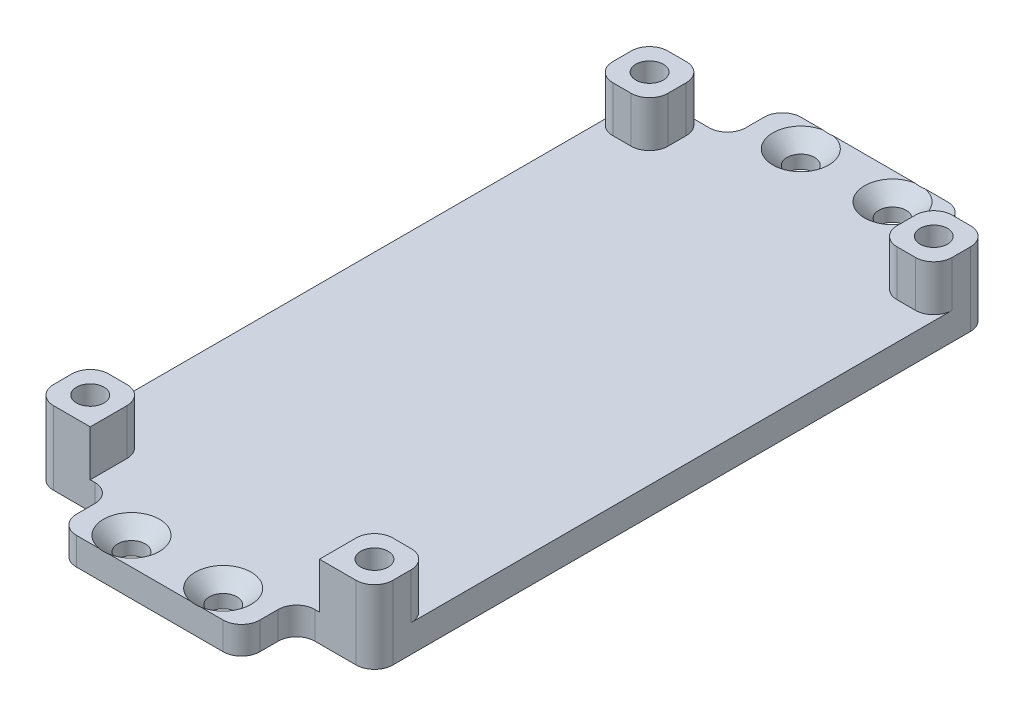
SolidWorks part; units mm, degrees
ref_plane "Front Plane" through (0, 0, 0) normal (0, 0, 1) x (1, 0, 0)
ref_plane "Top Plane" through (0, 0, 0) normal (0, 1, 0) x (1, 0, 0)
ref_plane "Right Plane" through (0, 0, 0) normal (1, 0, 0) x (0, 0, -1)
sketch "Sketch1" plane through (0, 0, 0) normal (0, 1, 0) x (1, 0, 0)
  line L0 (-36, 33) -> (0, 33) construction
  line L1 (0, 0) -> (-36, 0) construction
  line L2 (0, 0) -> (0, 66) construction
  line L3 (0, 66) -> (-36, 66) construction
  line L4 (-36, 0) -> (-36, 66) construction
  line L5 (-36.5, 66.5) -> (0.5, 66.5)
  line L6 (-36.5, 66.5) -> (-36.5, -0.5)
  line L7 (-36.5, -0.5) -> (0.5, -0.5)
  line L8 (0.5, 66.5) -> (0.5, -0.5)
  line L9 (-18, 66) -> (-18, 0) construction
  line L10 (-2.5, 63.5) -> (-33.5, 63.5) construction
  line L11 (-33.5, 2.5) -> (-33.5, 63.5) construction
  line L12 (-2.5, 2.5) -> (-33.5, 2.5) construction
  line L13 (-2.5, 2.5) -> (-2.5, 63.5) construction
  circle A4 centre (-2.5, 63.5) radius 1.5
  circle A5 centre (-33.5, 63.5) radius 1.5
  circle A6 centre (-2.5, 2.5) radius 1.5
  circle A7 centre (-33.5, 2.5) radius 1.5
  point P8 (0, 0)
  point P22 (0, 0)
  dimension "D3" = 3
  dimension "D1" = 66
  dimension "D2" = 36
  dimension "D4" = 67
  dimension "D5" = 37
  dimension "D6" = 2.5
extrude "Boss-Extrude1" add sketch "Sketch1" along normal blind 3
sketch "Sketch2" plane through (0, 3, 0) normal (0, 1, 0) x (1, 0, 0)
  line L0 (-36, 33) -> (0, 33) construction
  line L1 (-36.5, 66.5) -> (-30.5, 66.5)
  line L2 (-36.5, 66.5) -> (-36.5, 60.5)
  line L3 (-36.5, 60.5) -> (-30.5, 60.5)
  line L4 (-30.5, 66.5) -> (-30.5, 60.5)
  line L6 (-18, 66) -> (-18, 0) construction
  line L7 (-36, 33) -> (0, 33) construction
  line L9 (-18, 66) -> (-18, 0) construction
  line L10 (0.5, 60.5) -> (-5.5, 60.5)
  line L11 (-5.5, 66.5) -> (-5.5, 60.5)
  line L12 (0.5, 66.5) -> (-5.5, 66.5)
  line L13 (0.5, 66.5) -> (0.5, 60.5)
  line L30 (0.5, -0.5) -> (0.5, 5.5)
  line L31 (0.5, -0.5) -> (-5.5, -0.5)
  line L32 (-5.5, -0.5) -> (-5.5, 5.5)
  line L33 (0.5, 5.5) -> (-5.5, 5.5)
  line L34 (-36.5, 5.5) -> (-30.5, 5.5)
  line L35 (-30.5, -0.5) -> (-30.5, 5.5)
  line L36 (-36.5, -0.5) -> (-30.5, -0.5)
  line L37 (-36.5, -0.5) -> (-36.5, 5.5)
  circle A16 centre (-33.5, 2.5) radius 1.5 construction
  circle A17 centre (-2.5, 2.5) radius 1.5 construction
  circle A18 centre (-2.5, 63.5) radius 1.5 construction
  circle A19 centre (-33.5, 63.5) radius 1.5 construction
  circle A20 centre (-33.5, 2.5) radius 1.5
  circle A21 centre (-2.5, 2.5) radius 1.5
  circle A22 centre (-2.5, 63.5) radius 1.5
  circle A23 centre (-33.5, 63.5) radius 1.5
  point P6 (0, 0)
  dimension "D1" = 6
  dimension "D2" = 6
extrude "Boss-Extrude2" add sketch "Sketch2" along normal blind 5
fillet "Fillet1" radius 2 14 edges at (-30.5, 5.5, -60.5) (0.5, 4, -66.5) (0.5, 5.5, -60.5) (-5.5, 5.5, -66.5) (-5.5, 5.5, -60.5) (-30.5, 5.5, -66.5) (-36.5, 5.5, -60.5) (0.5, 5.5, -5.5) (-5.5, 5.5, -5.5) (-30.5, 5.5, -5.5) (-36.5, 5.5, -5.5) (-36.5, 4, 0.5) (0.5, 4, 0.5) (-36.5, 4, -66.5)
sketch "Sketch3" plane through (0, 3, 0) normal (0, 1, 0) x (1, 0, 0)
  line L0 (-36.5, 33) -> (0.5, 33) construction
  line L1 (-36.5, 62.5) -> (-36.5, 3.5) construction
  line L3 (0.5, 62.5) -> (0.5, 3.5) construction
  line L7 (-36.5, 43) -> (-42.5, 43)
  line L8 (-36.5, 43) -> (-36.5, 23)
  line L9 (-36.5, 23) -> (-42.5, 23)
  line L10 (-42.5, 43) -> (-42.5, 23)
  line L14 (-39.5, 43) -> (-39.5, 23) construction
  line L15 (-18, 66.5) -> (-18, -0.5) construction
  line L16 (-32.5, 66.5) -> (-3.5, 66.5) construction
  line L17 (-30.5, -0.5) -> (-5.5, -0.5) construction
  line L18 (0.5, 23) -> (6.5, 23)
  line L19 (6.5, 43) -> (6.5, 23)
  line L20 (0.5, 43) -> (6.5, 43)
  line L21 (0.5, 43) -> (0.5, 23)
  line L22 (-28, 69.5) -> (-8, 69.5) construction
  line L23 (-28, 66.5) -> (-8, 66.5)
  line L24 (-28, 66.5) -> (-28, 72.5)
  line L25 (-28, 72.5) -> (-8, 72.5)
  line L26 (-8, 66.5) -> (-8, 72.5)
  line L27 (-28, -3.5) -> (-8, -3.5) construction
  line L28 (-8, -0.5) -> (-8, -6.5)
  line L29 (-28, -6.5) -> (-8, -6.5)
  line L30 (-28, -0.5) -> (-28, -6.5)
  line L31 (-28, -0.5) -> (-8, -0.5)
  circle A0 centre (-39.5, 38) radius 1.5
  circle A1 centre (-39.5, 28) radius 1.5
  circle A4 centre (3.5, 28) radius 1.5
  circle A5 centre (3.5, 38) radius 1.5
  circle A6 centre (-13, 69.5) radius 1.5
  circle A7 centre (-23, 69.5) radius 1.5
  circle A8 centre (-23, -3.5) radius 1.5
  circle A9 centre (-13, -3.5) radius 1.5
  point P41 (0, 0)
  dimension "D3" = 3
  dimension "D7" = 3
  dimension "D1" = 20
  dimension "D2" = 6
  dimension "D4" = 5
  dimension "D5" = 6
  dimension "D6" = 20
  dimension "D8" = 5
extrude "Boss-Extrude3" add sketch "Sketch3" against normal up to surface (3 mm away) contours L28 L29 L30 L31 | L24 L23 L26 L25 | A7 | A6 | A8 | A9 up to face at (-33.5, 0, -1)
fillet "Fillet2" radius 2 8 edges at (-28, 1.5, -66.5) (-28, 1.5, -72.5) (-8, 1.5, -72.5) (-8, 1.5, -66.5) (-8, 1.5, 0.5) (-8, 1.5, 6.5) (-28, 1.5, 6.5) (-28, 1.5, 0.5)
chamfer "Chamfer1" distance 1.55 angle 45 4 edges at (-23, 3, -68) (-13, 3, -68) (-23, 3, 2) (-13, 3, 2)
